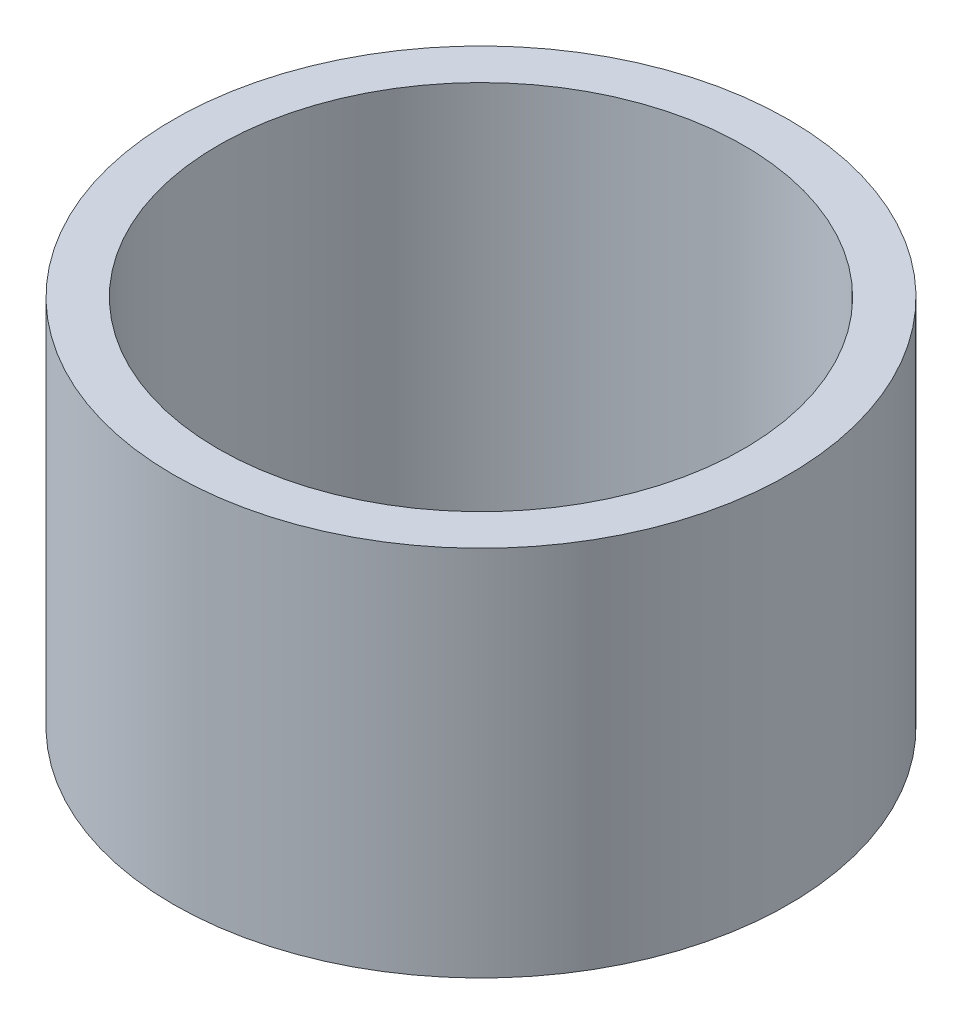
SolidWorks part; units mm, degrees
ref_plane "Front Plane" through (0, 0, 0) normal (0, 0, 1) x (1, 0, 0)
ref_plane "Top Plane" through (0, 0, 0) normal (0, 1, 0) x (1, 0, 0)
ref_plane "Right Plane" through (0, 0, 0) normal (1, 0, 0) x (0, 0, -1)
sketch "Sketch1" plane through (0, 0, 0) normal (0, 1, 0) x (1, 0, 0)
  circle A0 centre (0, 0) radius 20
  dimension "SLEEVE_OD" = 40
extrude "Boss-Extrude1" add sketch "Sketch1" along normal blind 24.1982
sketch "Sketch2" plane through (0, 0, 0) normal (0, 1, 0) x (1, 0, 0)
  circle A0 centre (0, 0) radius 17.0872
  dimension "BORE_D" = 34.1745
extrude "Cut-Extrude1" cut sketch "Sketch2" along normal through all
chamfer "Chamfer1" distance 3.605 angle 32.414 rebuild error yes
